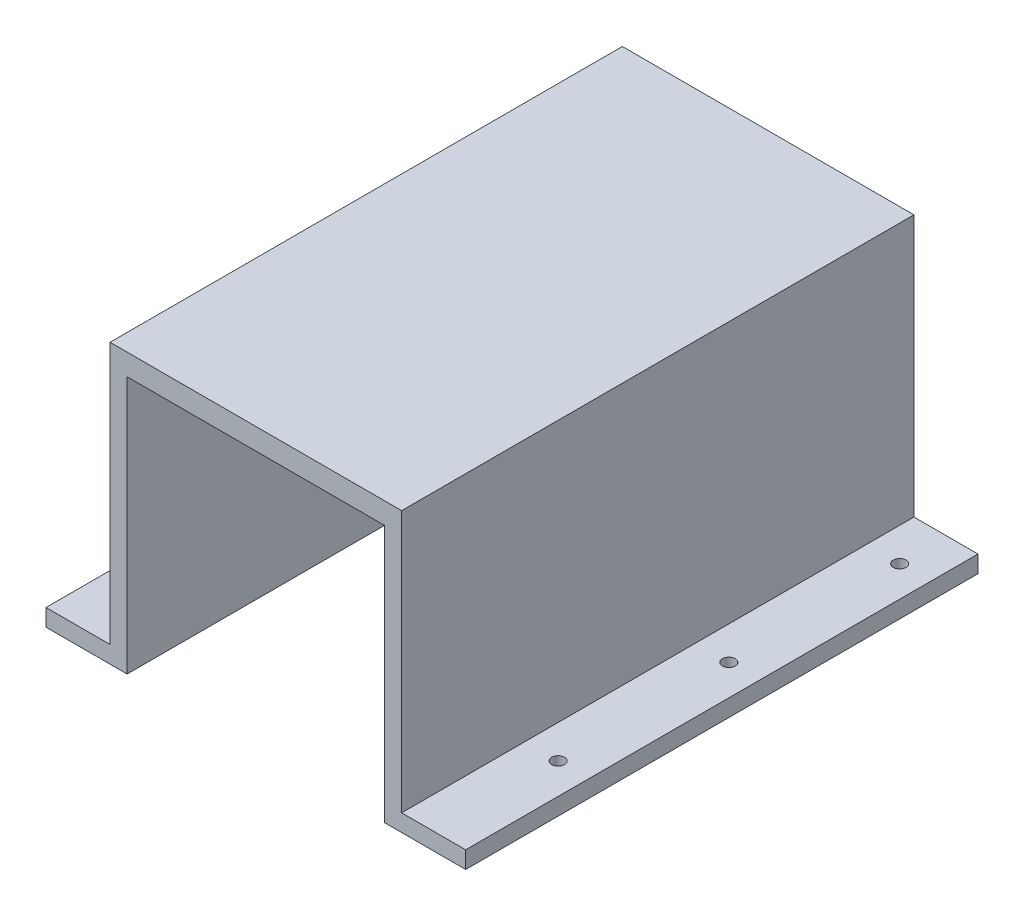
SolidWorks part; units mm, degrees
ref_plane "Front Plane" through (0, 0, 0) normal (0, 0, 1) x (1, 0, 0)
ref_plane "Top Plane" through (0, 0, 0) normal (0, 1, 0) x (1, 0, 0)
ref_plane "Right Plane" through (0, 0, 0) normal (1, 0, 0) x (0, 0, -1)
sketch "Sketch1" plane through (0, 0, 0) normal (0, 0, 1) x (1, 0, 0)
  line L0 (-49.15, 0) -> (57.9375, 0) construction
  line L1 (-34.15, 4) -> (-34.15, 65.3)
  line L2 (-34.15, 65.3) -> (34.15, 65.3)
  line L3 (-34.15, 0) -> (-30.15, 0)
  line L4 (-30.15, 0) -> (-30.15, 60.3)
  line L5 (-30.15, 60.3) -> (30.15, 60.3)
  line L7 (0, 0) -> (0, 42.8438) construction
  line L8 (34.15, 0) -> (30.15, 0)
  line L9 (30.15, 0) -> (30.15, 60.3)
  line L10 (34.15, 4) -> (34.15, 65.3)
  line L11 (-34.15, 4) -> (-49.15, 4)
  line L12 (-49.15, 4) -> (-49.15, 0)
  line L13 (-49.15, 0) -> (-34.15, 0)
  line L14 (49.15, 0) -> (34.15, 0)
  line L15 (49.15, 4) -> (49.15, 0)
  line L16 (34.15, 4) -> (49.15, 4)
  dimension "D1" = 68.3
  dimension "D2" = 60.3
  dimension "D4" = 60.3
  dimension "D5" = 15
  dimension "D6" = 4
  dimension "D7" = 5
  dimension "D9" = 4
extrude "Boss-Extrude1" add sketch "Sketch1" along normal blind 60 and the other way blind 60
sketch "Sketch2" plane through (0, 4, 0) normal (0, 1, 0) x (1, 0, 0)
  line L0 (49.15, -60) -> (34.15, -60) construction
  line L1 (49.15, 60) -> (49.15, -60) construction
  circle A0 centre (41.9466, -31.1484) radius 1.5
  circle A1 centre (41.9466, 8.8516) radius 1.5
  circle A2 centre (41.9466, 48.8516) radius 1.5
  dimension "D1" = 3
  dimension "D2" = 3
  dimension "D3" = 3
  dimension "D4" = 28.8516
  dimension "D5" = 7.2034
  dimension "D6" = 40
  dimension "D7" = 40
  dimension "D8" = 7.2034
  dimension "D9" = 7.2034
extrude "Cut-Extrude1" cut sketch "Sketch2" against normal through all
ref_plane "Plane1" through (0, 0, 0) normal (1, 0, 0) x (0, 0, -1)
mirror "Mirror1" about plane through (0, 0, 0) normal (1, 0, 0) of "Cut-Extrude1"
